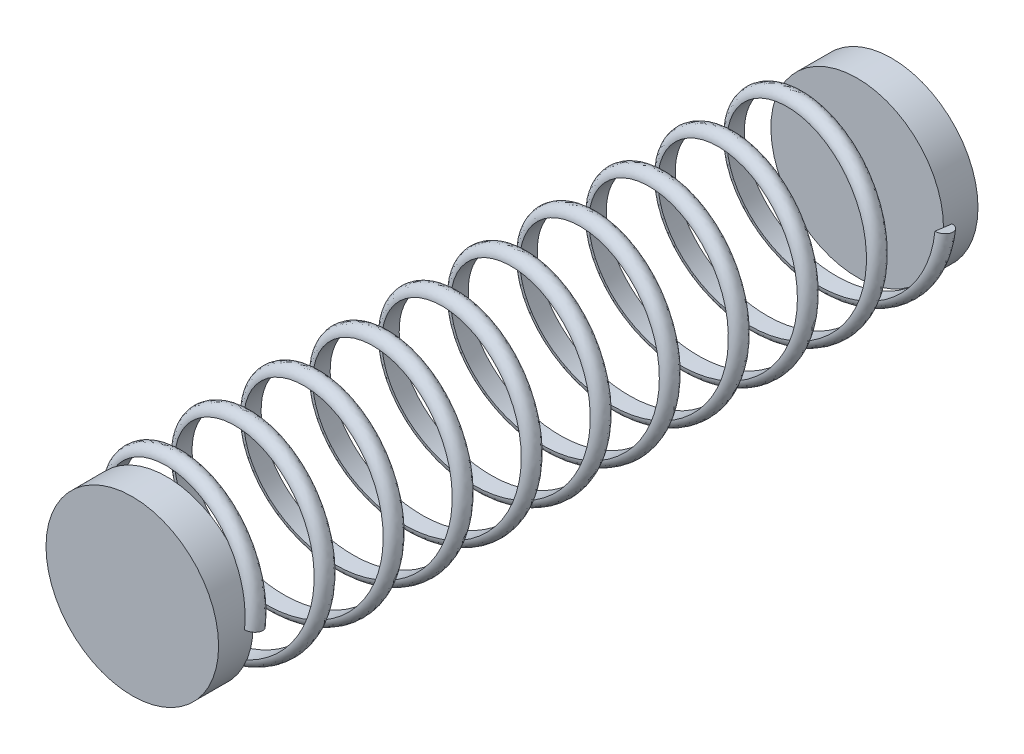
SolidWorks part; units mm, degrees
ref_plane "前视基准面" through (0, 0, 0) normal (0, 0, 1) x (1, 0, 0)
ref_plane "上视基准面" through (0, 0, 0) normal (0, 1, 0) x (1, 0, 0)
ref_plane "右视基准面" through (0, 0, 0) normal (1, 0, 0) x (0, 0, -1)
sketch "草图1" plane through (0, 0, 0) normal (0, 0, 1) x (1, 0, 0)
  circle A0 centre (0, 0) radius 5
curve "螺旋线/涡状线1" pitch 4 height 40 turns 10
sketch "草图2" plane through (0, 0, 0) normal (0, 1, 0) x (1, 0, 0)
  circle A0 centre (9.989, 0) radius 1
sweep "扫描1" add path "螺旋线/涡状线1" circular profile diameter 1 parameters "D3"=1
sketch "草图15" plane through (0, 0, 0) normal (0, 0, 1) x (1, 0, 0)
  circle A0 centre (0, 0) radius 5
extrude "凸台-拉伸1" add sketch "草图15" against normal blind 2 and the other way blind 42
sketch "草图16" plane through (0, 0, 0) normal (0, 0, 1) x (1, 0, 0)
  circle A0 centre (0, 0) radius 5
extrude "切除-拉伸1" cut sketch "草图16" along normal blind 40
